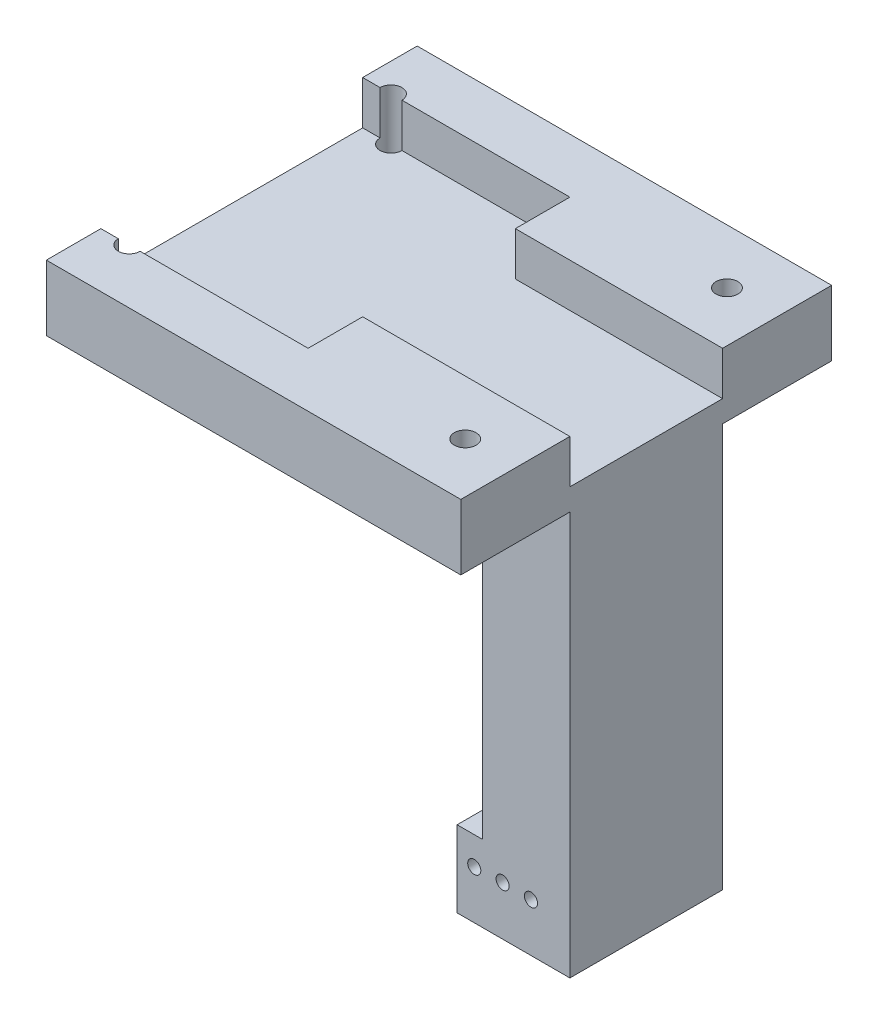
SolidWorks part; units mm, degrees
material "Copper"
ref_plane "Front Plane" through (0, 0, 0) normal (0, 0, 1) x (1, 0, 0)
ref_plane "Top Plane" through (0, 0, 0) normal (0, 1, 0) x (1, 0, 0)
ref_plane "Right Plane" through (0, 0, 0) normal (1, 0, 0) x (0, 0, -1)
sketch "Sketch3" plane through (0, 0, 0) normal (0, 0, 1) x (1, 0, 0)
  line L0 (-2.0815, 1.0718) -> (2.0865, 1.0718)
  line L1 (-2.0815, 1.0718) -> (-2.0815, -1.4282)
  line L2 (-2.0815, -1.4282) -> (2.0865, -1.4282)
  line L3 (2.0865, -1.4282) -> (2.0865, 1.0718)
  line L4 (-2.0815, 1.0718) -> (2.0865, -1.4282) construction
  line L5 (-2.0815, -1.4282) -> (2.0865, 1.0718) construction
  circle A0 centre (-1.2975, -0.2085) radius 0.3
  circle A1 centre (0.0025, -0.1782) radius 0.3
  circle A2 centre (1.3025, -0.2085) radius 0.3
  dimension "D5" = 0.6
  dimension "D3" = 1.3
  dimension "D4" = 1.3
  dimension "D6" = 2.5
extrude "Boss-Extrude1" add sketch "Sketch3" along normal blind 3 contours L0 L1 L2 A2 A1 A0 region at (0.0025, 1.0232, 0)
sketch "Sketch6" plane through (0, 0, 0) normal (0, 0, 1) x (1, 0, 0)
  line L0 (2.0865, 1.0718) -> (-0.9135, 1.0718)
  line L1 (-0.9135, 16.0718) -> (-0.9135, 1.0718)
  line L2 (2.0865, 16.0718) -> (-0.9135, 16.0718)
  line L5 (-15.9135, 17.0718) -> (-15.9135, 16.0718)
  line L6 (-15.9135, 16.0718) -> (2.0865, 16.0718)
  line L7 (2.0865, 16.0718) -> (2.0865, 1.0718)
  line L8 (2.0865, 16.0718) -> (2.0865, 17.0718)
  line L9 (2.0865, 16.0718) -> (-0.9135, 16.0718)
  line L10 (2.0865, 17.0718) -> (-15.9135, 17.0718)
  dimension "D1" = 3
  dimension "D2" = 15
  dimension "D3" = 1
  dimension "D4" = 18
extrude "Boss-Extrude3" add sketch "Sketch6" along normal blind 3
extrude "Boss-Extrude4" add sketch "Sketch6<5>" along normal blind 8 contours L6 L9 L5 region at (-6.9135, 16.5718, 0)
sketch "Sketch6<5>" plane through (0, 0, 0) normal (0, 0, 1) x (1, 0, 0) same geometry as "Sketch6"
ref_plane "Plane1" through (0, 0, -0.5) normal (0, 0, -1) x (-1, 0, 0)
mirror "Mirror4" about plane through (0, 0, -0.5) normal (0, 0, -1) of bodies 105
sketch "Sketch7" plane through (0, 17.0718, 0) normal (0, 1, 0) x (1, 0, 0)
  line L0 (-14.6135, -5.5) -> (-14.6135, 6.5) construction
  line L2 (-14.6135, -5.5) -> (-14.6135, -8) construction
  line L3 (2.0865, -8) -> (-15.9135, -8) construction
  line L4 (-14.6135, 6.5) -> (-14.6135, 9) construction
  line L5 (2.0865, 9) -> (-15.9135, 9) construction
  line L6 (0.7865, -5.5) -> (0.7865, 6.5) construction
  line L7 (0.7865, -5.5) -> (2.0865, -5.5) construction
  line L8 (2.0865, -8) -> (2.0865, 0) construction
  line L9 (-14.6135, -5.5) -> (-15.9135, -5.5) construction
  line L10 (-15.9135, -8) -> (-15.9135, 0) construction
  circle A0 centre (-14.6135, -5.5) radius 0.5
  circle A1 centre (-14.6135, 6.5) radius 0.5
  circle A2 centre (0.7865, -5.5) radius 0.5
  circle A3 centre (0.7865, 6.5) radius 0.5
  dimension "D1" = 1
  dimension "D2" = 1
  dimension "D3" = 12
  dimension "D4" = 2
extrude "Cut-Extrude1" cut sketch "Sketch7" against normal blind 1
sketch "Sketch8" plane through (0, 0, -0.5) normal (0, 0, -1) x (-1, 0, 0)
  line L0 (2.0815, -1.4282) -> (2.0815, -2.4282)
  line L1 (2.0815, -2.4282) -> (-2.0865, -2.4282)
  line L2 (-2.0865, -1.4282) -> (-2.0865, -2.4282)
  line L3 (2.0815, -1.4282) -> (-2.0865, -1.4282)
  line L4 (0.9135, 1.0718) -> (-2.0865, 1.0718)
  line L5 (-2.0865, -1.4282) -> (-2.0865, 17.0718) construction
  line L6 (-2.0865, 17.0718) -> (-3.0865, 17.0718)
  line L7 (-3.0865, 17.0718) -> (-3.0865, -2.4282)
  line L8 (-3.0865, -2.4282) -> (-2.0865, -2.4282)
  line L9 (-3.0865, 16.0718) -> (-2.0865, 16.0718)
  line L14 (15.9135, 17.0718) -> (-2.0865, 17.0718)
  line L15 (-2.0865, 17.0718) -> (-2.0865, -1.4282)
  line L16 (-2.0865, -1.4282) -> (2.0815, -1.4282)
  line L17 (2.0815, -1.4282) -> (2.0815, 1.0718)
  line L18 (2.0815, 1.0718) -> (0.9135, 1.0718)
  line L19 (0.9135, 1.0718) -> (0.9135, 16.0718)
  line L20 (0.9135, 16.0718) -> (15.9135, 16.0718)
  line L21 (15.9135, 16.0718) -> (15.9135, 17.0718)
  line L22 (15.9135, 17.0718) -> (-2.0865, 17.0718)
  line L23 (-2.0865, 17.0718) -> (-2.0865, -1.4282)
  line L24 (-2.0865, -1.4282) -> (2.0815, -1.4282)
  line L25 (2.0815, -1.4282) -> (2.0815, 1.0718)
  line L26 (2.0815, 1.0718) -> (0.9135, 1.0718)
  line L27 (0.9135, 1.0718) -> (0.9135, 16.0718)
  line L28 (0.9135, 16.0718) -> (15.9135, 16.0718)
  line L29 (15.9135, 16.0718) -> (15.9135, 17.0718)
  dimension "D1" = 1
  dimension "D2" = 0
extrude "Boss-Extrude5" add sketch "Sketch8" along normal blind 1 and the other way blind 1 contours L28 L29 L22 L23 L4 L27 | L23 L6 L7 L8 L2 | L0 L3 L2 L1 | L23 L6 L7 L9 region at (0.0025, -1.9282, -0.5) region at (2.5865, 6.8218, -0.5) region at (1.8456, 8.5718, -0.5) region at (2.5865, 16.5718, -0.5)
extrude "Boss-Extrude6" add sketch "Sketch8<5>" along normal blind 3.5 and the other way blind 3.5 contours L0 L3 L2 L1 region at (0.0025, -1.9282, -0.5)
sketch "Sketch8<5>" plane through (0, 0, -0.5) normal (0, 0, -1) x (-1, 0, 0) same geometry as "Sketch8"
extrude "Boss-Extrude7" add sketch "Sketch8<6>" along normal blind 3.5 and the other way blind 3.5 contours L23 L6 L7 L8 L2 region at (2.5865, 6.8218, -0.5)
sketch "Sketch8<6>" plane through (0, 0, -0.5) normal (0, 0, -1) x (-1, 0, 0) same geometry as "Sketch8"
sketch "Sketch9" plane through (0, 17.0718, 0) normal (0, 1, 0) x (1, 0, 0)
  line L0 (-6.4135, 4) -> (-6.4135, 6.5)
  line L1 (-6.4135, 4) -> (3.0865, 4)
  line L2 (3.0865, -0.5) -> (3.0865, 1.5) construction
  line L3 (3.0865, 4) -> (3.0865, 9)
  line L4 (3.0865, 9) -> (-15.9135, 9)
  line L5 (-15.9135, -8) -> (-15.9135, 9) construction
  line L6 (-15.9135, 9) -> (-15.9135, 6.5)
  line L7 (2.0865, 9) -> (-15.9135, 9) construction
  line L8 (2.0865, -8) -> (-15.9135, -8) construction
  line L9 (-15.9135, -8) -> (3.0865, -8)
  line L10 (3.0865, -8) -> (3.0865, -3)
  line L11 (3.0865, -3) -> (-6.4135, -3)
  line L12 (-15.9135, -5.5) -> (-15.9135, -8)
  line L13 (-6.4135, -3) -> (-6.4135, -5.5)
  line L14 (-6.4135, -5.5) -> (-15.9135, -5.5)
  line L15 (-6.4135, 6.5) -> (-15.9135, 6.5)
  line L16 (0.7865, -5.5) -> (3.0865, -5.5) construction
  circle A0 centre (-14.6135, -5.5) radius 0.5 construction
  circle A1 centre (-14.6135, 6.5) radius 0.5 construction
  circle A2 centre (0.7865, 6.5) radius 0.5 construction
  circle A3 centre (0.7865, -5.5) radius 0.5 construction
  circle A4 centre (-14.6135, -5.5) radius 0.5
  circle A5 centre (-14.6135, 6.5) radius 0.5
  circle A6 centre (0.7865, 6.5) radius 0.5
  circle A7 centre (0.7865, -5.5) radius 0.5
  point P15 (-14.6135, 6.5)
  point P26 (-14.6135, -5.5)
  line M4 (2.0865, 9) -> (-15.9135, 9)
  line M5 (-15.9135, 9) -> (-15.9135, -8)
  line M6 (-15.9135, -8) -> (2.0865, -8)
  circle M7 centre (0.7865, -5.5) radius 0.5
  circle M8 centre (-14.6135, -5.5) radius 0.5
  circle M9 centre (0.7865, 6.5) radius 0.5
  circle M10 centre (-14.6135, 6.5) radius 0.5
  line M38 (2.0865, 1.5) -> (2.0865, 9)
  line M39 (2.0865, -8) -> (2.0865, -0.5)
extrude "Boss-Extrude8" add sketch "Sketch9" along normal blind 2 contours L11 L13 L14 M7 M39 M8 M5 M6 | L16 L10 L11 M39 | L16 L9 L10 M39 | L15 L0 L1 M38 M4 M5 M10 M9 | L3 L4 L1 M38 region at (-5.4088, 17.0718, 5.9549) region at (-5.4088, 17.0718, -6.9549) region at (2.5865, 17.0718, -6.5) region at (2.5865, 17.0718, 6.75) region at (2.5865, 17.0718, 4.25)
extrude "Boss-Extrude9" add sketch "Sketch8<7>" along normal blind 8.5 and the other way blind 8.5 contours L23 L6 L7 L9 region at (2.5865, 16.5718, -0.5)
sketch "Sketch8<7>" plane through (0, 0, -0.5) normal (0, 0, -1) x (-1, 0, 0) same geometry as "Sketch8"
